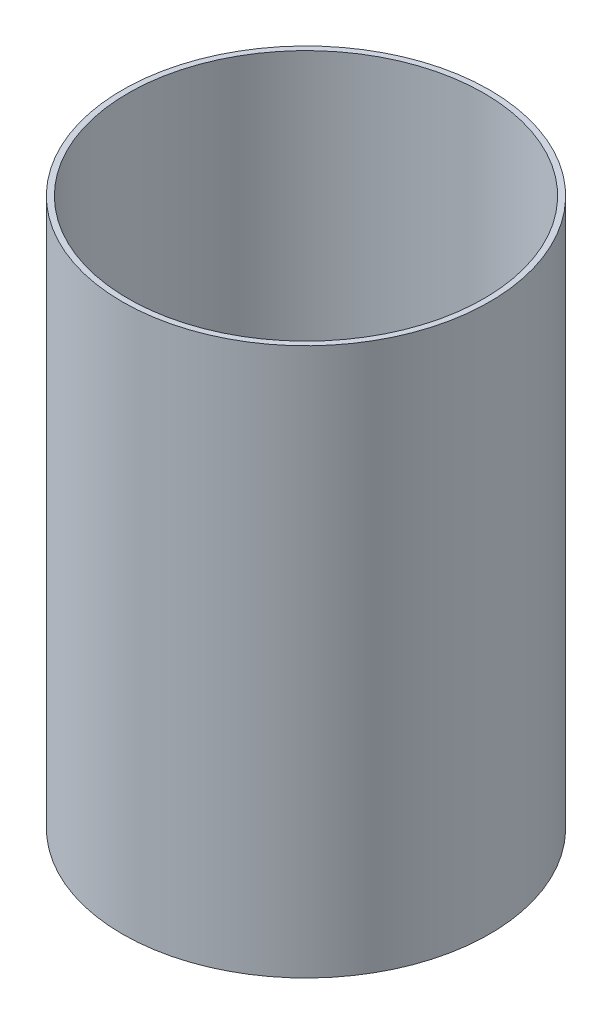
SolidWorks part; units mm, degrees
ref_plane "Front Plane" through (0, 0, 0) normal (0, 0, 1) x (1, 0, 0)
ref_plane "Top Plane" through (0, 0, 0) normal (0, 1, 0) x (1, 0, 0)
ref_plane "Right Plane" through (0, 0, 0) normal (1, 0, 0) x (0, 0, -1)
sketch "Sketch1" plane through (0, 0, 0) normal (0, 1, 0) x (1, 0, 0)
  circle A0 centre (0, 0) radius 51.1048
  circle A1 centre (0, 0) radius 49.53
  dimension "D1" = 102.2096
  dimension "D2" = 99.06
extrude "Boss-Extrude1" add sketch "Sketch1" along normal blind 152.4
equation "\"Body_Tube_OD\"= 4.024in"
equation "\"Body_Tube_ID\"= 3.90in"
equation "\"D1@Sketch1\"=\"Body_Tube_OD\""
equation "\"D2@Sketch1\"=\"Body_Tube_ID\""
equation "\"Mid_Section_Length\"= 6in"
equation "\"D1@Boss-Extrude1\"=\"Mid_Section_Length\""
